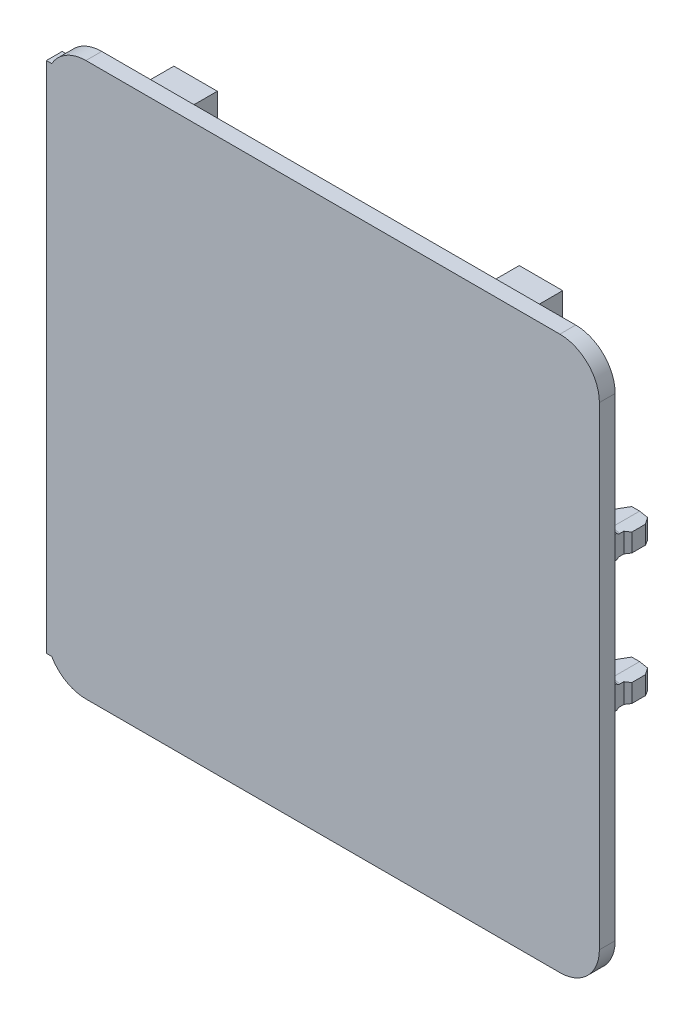
SolidWorks part; units mm, degrees
ref_plane "前视基准面" through (0, 0, 0) normal (0, 0, 1) x (1, 0, 0)
ref_plane "上视基准面" through (0, 0, 0) normal (0, 1, 0) x (1, 0, 0)
ref_plane "右视基准面" through (0, 0, 0) normal (1, 0, 0) x (0, 0, -1)
other "Configuration Table"
sketch "草图1" plane through (0, 0, 0) normal (0, 0, 1) x (1, 0, 0)
  line L0 (-30, -35) -> (30, -35) construction
  line L1 (35, -30) -> (35, 30) construction
  line L2 (30, 35) -> (-30, 35) construction
  line L3 (-30, -35) -> (30, -35)
  line L4 (35, -30) -> (35, 30)
  line L5 (30, 35) -> (-30, 35)
  line L9 (-35.8467, -30) -> (-34.8301, -30) construction
  line L10 (-35, -30) -> (-35, 30)
  line L11 (-35, -30) -> (-35, -32.5)
  line L12 (-34.3301, -32.5) -> (-35.8467, -32.5) construction
  line L13 (-35, -32.5) -> (-34.3301, -32.5)
  line L14 (-35, 30) -> (-35, 32.5)
  line L15 (-34.3301, 32.5) -> (-35.8467, 32.5) construction
  line L16 (-35, 32.5) -> (-34.3301, 32.5)
  arc A0 (30, -35) -> (35, -30) centre (30, -30) ccw construction
  arc A1 (35, 30) -> (30, 35) centre (30, 30) ccw construction
  arc A2 (30, -35) -> (35, -30) centre (30, -30) ccw
  arc A3 (35, 30) -> (30, 35) centre (30, 30) ccw
  arc A4 (-30, 35) -> (-34.3301, 32.5) centre (-30, 30) ccw
  arc A5 (-34.3301, -32.5) -> (-30, -35) centre (-30, -30) ccw
  arc A6 (-34.3301, -32.5) -> (-30, -35) centre (-30, -30) ccw construction
extrude "凸台-拉伸1" add sketch "草图1" along normal blind 2
sketch "草图2" plane through (0, 0, 0) normal (0, 0, -1) x (-1, 0, 0)
  line L0 (25.8672, -32.95) -> (25.8672, -29.95)
  line L1 (20.3672, -29.95) -> (20.3672, -32.95)
  line L2 (20.3672, -32.95) -> (25.8672, -32.95)
  line L3 (30, -35) -> (-30, -35) construction
  line L4 (20.3672, 32.95) -> (20.3672, 29.95)
  line L5 (25.8672, 29.95) -> (25.8672, 32.95)
  line L6 (25.8672, 32.95) -> (20.3672, 32.95)
  line L7 (-30, 35) -> (30, 35) construction
  line L8 (-23.357, -29.95) -> (-23.357, -32.95)
  line L9 (-23.357, -32.95) -> (-17.857, -32.95)
  line L10 (-17.857, -32.95) -> (-17.857, -29.95)
  line L11 (-23.357, 32.95) -> (-17.857, 32.95)
  line L12 (-17.857, 32.95) -> (-17.857, 29.95)
  line L13 (-23.357, 29.95) -> (-23.357, 32.95)
  arc A0 (25.8672, -29.95) -> (20.3672, -29.95) centre (23.1172, -29.95) ccw
  arc A1 (20.3672, 29.95) -> (25.8672, 29.95) centre (23.1172, 29.95) ccw
  arc A2 (-17.857, -29.95) -> (-23.357, -29.95) centre (-20.607, -29.95) ccw
  arc A3 (-17.857, 29.95) -> (-23.357, 29.95) centre (-20.607, 29.95) cw
  dimension "D1" = 2.05
  dimension "D2" = 3
  dimension "D3" = 5.5
  dimension "D4" = 2.05
  dimension "D5" = 5.5
  dimension "D6" = 3
  dimension "D7" = 2.05
  dimension "D8" = 5.5
  dimension "D9" = 3
  dimension "D10" = 5.5
  dimension "D11" = 2.05
  dimension "D12" = 3
extrude "凸台-拉伸2" add sketch "草图2" along normal blind 5
sketch "草图3" plane through (0, 0, 0) normal (0, 0, -1) x (-1, 0, 0)
  line L0 (30, -35) -> (-30, -35) construction
  line L1 (32.9, -29.95) -> (30.9, -29.95)
  line L2 (32.9, -29.95) -> (32.9, -28.05)
  line L3 (32.9, -28.05) -> (30.9, -28.05)
  line L4 (30.9, -29.95) -> (30.9, -28.05)
  line L5 (35, 32.5) -> (35, -32.5) construction
  line L6 (-30, 35) -> (30, 35) construction
  line L7 (32.9, 22.95) -> (30.9, 22.95)
  line L8 (32.9, 22.95) -> (32.9, 20.05)
  line L9 (32.9, 20.05) -> (30.9, 20.05)
  line L10 (30.9, 22.95) -> (30.9, 20.05)
  line L11 (-35, -30) -> (-35, 30) construction
  line L12 (-32.9, -4.05) -> (-30.9, -4.05)
  line L13 (-32.9, -4.05) -> (-32.9, -6.95)
  line L14 (-32.9, -6.95) -> (-30.9, -6.95)
  line L15 (-30.9, -4.05) -> (-30.9, -6.95)
  line L17 (-32.9, 12.45) -> (-30.9, 12.45)
  line L18 (-32.9, 12.45) -> (-32.9, 9.55)
  line L19 (-32.9, 9.55) -> (-30.9, 9.55)
  line L20 (-30.9, 12.45) -> (-30.9, 9.55)
  dimension "D1" = 2
  dimension "D2" = 1.9
  dimension "D3" = 5.05
  dimension "D4" = 2.1
  dimension "D5" = 2
  dimension "D6" = 2.9
  dimension "D7" = 12.05
  dimension "D8" = 2.1
  dimension "D9" = 2
  dimension "D10" = 2.9
  dimension "D11" = 28.05
  dimension "D12" = 2.1
  dimension "D13" = 2
  dimension "D14" = 2.9
  dimension "D15" = 2.1
  dimension "D16" = 22.55
extrude "凸台-拉伸3" add sketch "草图3" along normal blind 3.2
sketch "草图4" plane through (0, 0, -3.2) normal (0, 0, -1) x (-1, 0, 0)
  line L0 (32.9, -28.05) -> (30.9, -28.05) construction
  line L1 (30.9, -29.95) -> (34.05, -29.95)
  line L2 (30.9, -29.95) -> (30.9, -28.05)
  line L3 (30.9, -28.05) -> (34.05, -28.05)
  line L4 (34.05, -29.95) -> (34.05, -28.05)
  line L5 (30.9, 20.05) -> (34.05, 20.05)
  line L6 (30.9, 20.05) -> (30.9, 22.95)
  line L7 (30.9, 22.95) -> (34.05, 22.95)
  line L8 (34.05, 20.05) -> (34.05, 22.95)
  line L9 (32.9, 22.95) -> (30.9, 22.95) construction
  line L10 (-32.9, -6.95) -> (-30.9, -6.95) construction
  line L11 (-30.9, -4.05) -> (-33.9, -4.05)
  line L12 (-30.9, -4.05) -> (-30.9, -6.95)
  line L13 (-30.9, -6.95) -> (-33.9, -6.95)
  line L14 (-33.9, -4.05) -> (-33.9, -6.95)
  line L15 (-32.9, 9.55) -> (-30.9, 9.55) construction
  line L16 (-30.9, 12.45) -> (-33.9, 12.45)
  line L17 (-30.9, 12.45) -> (-30.9, 9.55)
  line L18 (-30.9, 9.55) -> (-33.9, 9.55)
  line L19 (-33.9, 12.45) -> (-33.9, 9.55)
  dimension "D1" = 3.15
  dimension "D2" = 3.15
  dimension "D3" = 3
  dimension "D4" = 3
extrude "凸台-拉伸4" add sketch "草图4" along normal blind 3
sketch "草图6" plane through (0, 0, -6.2) normal (0, 0, -1) x (-1, 0, 0)
  line L1 (30.9, 22.95) -> (34.05, 22.95)
  line L2 (30.9, 22.95) -> (30.9, 20.05)
  line L3 (30.9, 20.05) -> (34.05, 20.05)
  line L4 (34.05, 22.95) -> (34.05, 20.05)
  line L5 (30.9, -28.05) -> (34.05, -28.05)
  line L6 (30.9, -28.05) -> (30.9, -29.95)
  line L7 (30.9, -29.95) -> (34.05, -29.95)
  line L8 (34.05, -28.05) -> (34.05, -29.95)
extrude "凸台-拉伸5" add sketch "草图6" along normal blind 0.7
sketch "草图7" plane through (0, -29.95, 0) normal (0, -1, 0) x (1, 0, 0)
  line L0 (-30.9, -6.9) -> (-26.9163, 0)
  line L1 (-30, 0) -> (30, 0) construction
  line L2 (-26.9163, 0) -> (-30.9, 0)
  line L3 (-30.9, 0) -> (-30.9, -6.9)
  dimension "D1" = 60
extrude "凸台-拉伸6" add sketch "草图7" against normal up to surface (1.9 mm away) up to face at (-32.6167, -28.05, -3.3667)
sketch "草图8" plane through (0, 22.95, 0) normal (0, 1, 0) x (1, 0, 0)
  line L0 (-30.9, 6.9) -> (-26.9163, 0)
  line L1 (-26.9163, 0) -> (-30.9, 0)
  line L2 (-30.9, 0) -> (-30.9, 6.9)
extrude "凸台-拉伸7" add sketch "草图8" against normal up to surface (2.9 mm away) up to face at (-32.6167, 20.05, -3.3667)
sketch "草图9" plane through (0, 12.45, 0) normal (0, 1, 0) x (1, 0, 0)
  line L0 (30.9, 6.2) -> (27.3204, 0)
  line L1 (30, 0) -> (-30, 0) construction
  line L2 (27.3204, 0) -> (30.9, 0)
  line L3 (30.9, 0) -> (30.9, 6.2)
  dimension "D1" = 60
extrude "凸台-拉伸8" add sketch "草图9" against normal up to surface (2.9 mm away) up to face at (32.5667, 9.55, -3.1333)
sketch "草图10" plane through (0, -6.95, 0) normal (0, -1, 0) x (1, 0, 0)
  line L0 (30.9, -6.2) -> (27.3204, 0)
  line L1 (27.3204, 0) -> (30.9, 0)
  line L2 (30.9, 0) -> (30.9, -6.2)
extrude "凸台-拉伸9" add sketch "草图10" against normal up to surface (2.9 mm away) up to face at (32.5667, -4.05, -3.1333)
fillet "圆角1" radius 2 6 edges at (-29.9081, 20.05, 0) (-29.9081, 22.95, 0) (30.1102, 12.45, 0) (30.1102, -6.95, 0) (-29.9081, -29.95, 0) (-29.9081, -28.05, 0)
sketch "草图11" plane through (0, 12.45, 0) normal (0, 1, 0) x (1, 0, 0)
  line L0 (33.4, 3.2) -> (33.9, 3.7)
  line L1 (32.9, 3.2) -> (33.9, 3.2) construction
  line L2 (33.9, 6.2) -> (33.9, 3.2) construction
  line L3 (33.9, 3.7) -> (33.9, 3.2)
  line L4 (33.9, 3.2) -> (33.4, 3.2)
extrude "切除-拉伸1" cut sketch "草图11" against normal up to surface (19.4 mm away) up to face at (32.1625, -6.95, -3.8)
sketch "草图12" plane through (0, 0, 0) normal (0, 0, -1) x (-1, 0, 0)
  line L0 (-35, -30) -> (-35, 30) construction
  line L1 (-27.3, -1.7664) -> (-32, -1.7664)
  line L2 (-27.3, -1.7664) -> (-27.3, 7.2336)
  line L3 (-27.3, 7.2336) -> (-32, 7.2336)
  line L4 (-32, -1.7664) -> (-32, 7.2336)
  dimension "D1" = 3
  dimension "D2" = 4.7
  dimension "D3" = 9
extrude "凸台-拉伸10" add sketch "草图12" along normal blind 0.8
chamfer "倒角1" distance 1 angle 45 2 edges at (33.9, -5.5, -6.2) (33.9, 11, -6.2)
sketch "草图13" plane through (0, -6.95, 0) normal (0, -1, 0) x (1, 0, 0)
  line L0 (32.9, -3.2) -> (33.4, -3.7)
  line L1 (33.4, -3.7) -> (33.4, -5.4301)
  line L2 (33.4, -5.4301) -> (32.9, -6.2)
  line L3 (32.9, -6.2) -> (33.9, -5.2)
  line L4 (33.9, -5.2) -> (33.9, -3.7)
  line L5 (33.9, -3.7) -> (33.4, -3.2)
  line L6 (33.4, -3.2) -> (32.9, -3.2)
  line L7 (32.9, -6.2) -> (30.9, -6.2) construction
  line L8 (33, -1) -> (33, -9.5) construction
  dimension "D1" = 123
  dimension "D2" = 0.4
extrude "切除-拉伸2" cut sketch "草图13" against normal blind 20
sketch "草图14" plane through (0, 0, -6.2) normal (0, 0, -1) x (-1, 0, 0)
  line L0 (-33.4, 12.15) -> (-31.9, 12.45)
  line L1 (-33.4, 12.45) -> (-33.4, 9.55) construction
  line L2 (-28.4751, 12.45) -> (-32.9, 12.45) construction
  line L3 (-31.9, 12.45) -> (-33.4, 12.45)
  line L4 (-33.4, 12.45) -> (-33.4, 12.15)
  line L5 (-33.4, 9.55) -> (-33.4, 9.85)
  line L6 (-33.4, 9.85) -> (-31.9, 9.55)
  line L7 (-32.9, 9.55) -> (-27.3204, 9.55) construction
  line L8 (-31.9, 9.55) -> (-33.4, 9.55)
  line L9 (-33.4, -4.05) -> (-33.4, -4.35)
  line L10 (-33.4, -4.05) -> (-33.4, -6.95) construction
  line L11 (-33.4, -4.05) -> (-32.9, -4.05) construction
  line L12 (-33.4, -4.35) -> (-31.9, -4.05)
  line L13 (-30.9, -4.05) -> (-32.9, -4.05) construction
  line L14 (-31.9, -4.05) -> (-33.4, -4.05)
  line L15 (-33.4, -6.95) -> (-31.9, -6.95)
  line L16 (-32.9, -6.95) -> (-30.9, -6.95) construction
  line L17 (-31.9, -6.95) -> (-33.4, -6.65)
  line L18 (-33.4, -6.65) -> (-33.4, -6.95)
  dimension "D1" = 0.3
  dimension "D2" = 1.5
  dimension "D3" = 0.3
  dimension "D4" = 1.5
  dimension "D5" = 0.3
  dimension "D6" = 1.5
  dimension "D7" = 0.3
  dimension "D8" = 1.5
extrude "切除-拉伸3" cut sketch "草图14" against normal blind 4
fillet "圆角2" radius 0.5 4 edges at (32.4, 9.65, -2.2) (32.4, 12.35, -2.2) (32.4, -4.15, -2.2) (32.4, -6.85, -2.2)
